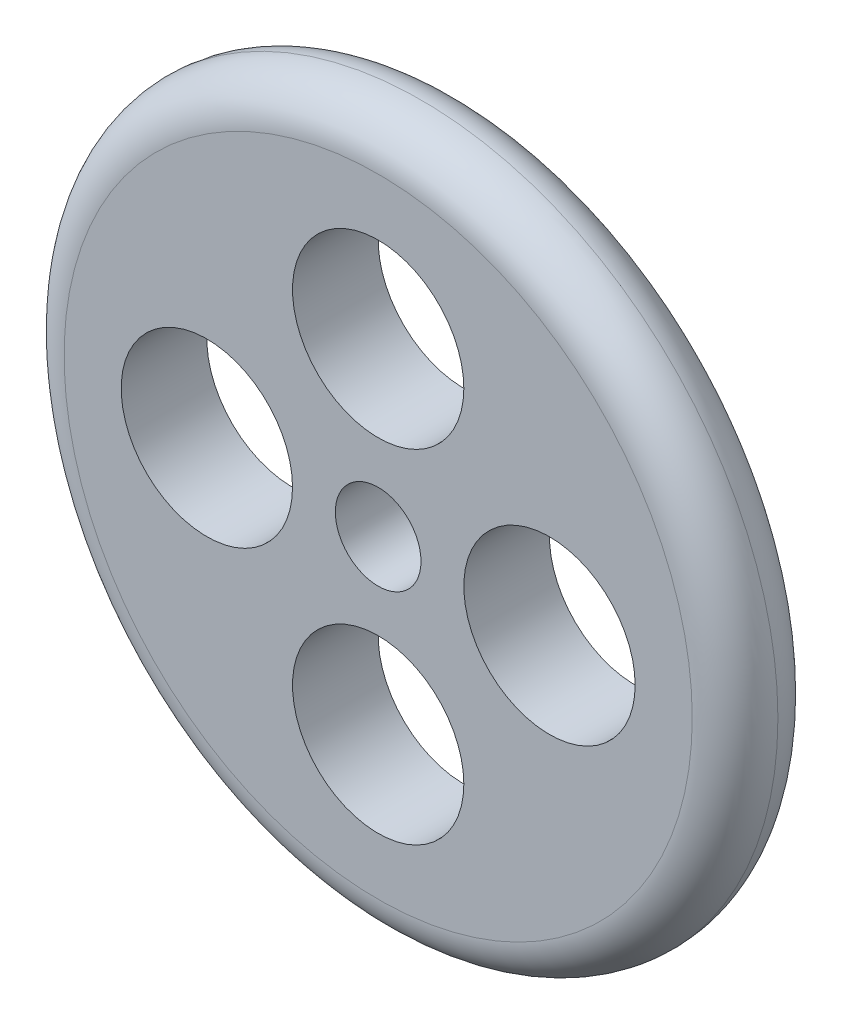
SolidWorks part; units mm, degrees
ref_plane "Front Plane" through (0, 0, 0) normal (0, 0, 1) x (1, 0, 0)
ref_plane "Top Plane" through (0, 0, 0) normal (0, 1, 0) x (1, 0, 0)
ref_plane "Right Plane" through (0, 0, 0) normal (1, 0, 0) x (0, 0, -1)
sketch "Sketch2" plane through (0, 0, 0) normal (0, 0, 1) x (1, 0, 0)
  circle A0 centre (0, 0) radius 125
  dimension "D1" = 250
extrude "Boss-Extrude1" add sketch "Sketch2" along normal blind 30
fillet "Fillet1" radius 15 2 edges at (125, 0, 0) (125, 0, 30)
sketch "Sketch3" plane through (0, 0, 30) normal (0, 0, 1) x (1, 0, 0)
  circle A0 centre (0, 0) radius 15
  dimension "D1" = 30
extrude "Cut-Extrude1" cut sketch "Sketch3" against normal through all
sketch "Sketch6" plane through (0, 0, 30) normal (0, 0, 1) x (1, 0, 0)
  circle A0 centre (0, 60) radius 30
  circle A1 centre (60, 0) radius 30
  circle A2 centre (0, -60) radius 30
  circle A3 centre (-60, 0) radius 30
  dimension "D2" = 60
  dimension "D4" = 60
  dimension "D6" = 60
  dimension "D8" = 60
  dimension "D1" = 60
  dimension "D3" = 60
  dimension "D5" = 60
  dimension "D7" = 60
extrude "Cut-Extrude2" cut sketch "Sketch6" against normal through all
